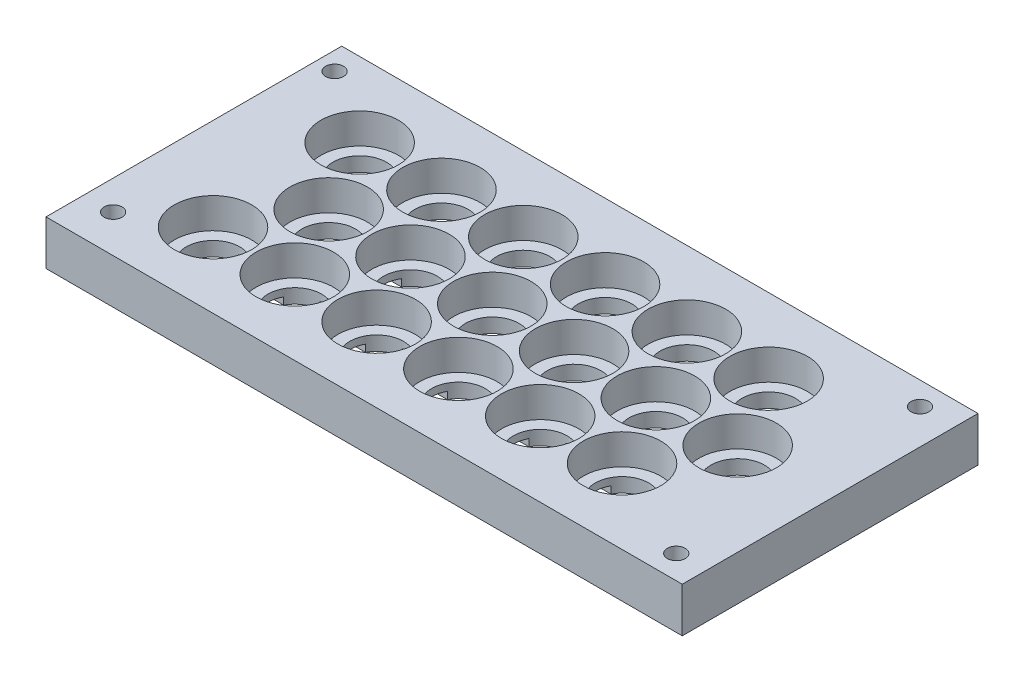
SolidWorks part; units mm, degrees
ref_plane "Front Plane" through (0, 0, 0) normal (0, 0, 1) x (1, 0, 0)
ref_plane "Top Plane" through (0, 0, 0) normal (0, 1, 0) x (1, 0, 0)
ref_plane "Right Plane" through (0, 0, 0) normal (1, 0, 0) x (0, 0, -1)
sketch "Sketch1" plane through (0, 0, 0) normal (0, 1, 0) x (1, 0, 0)
  line L0 (-11.825, 20.4815) -> (0, 0) construction
  line L5 (0, 0) -> (-11.825, -20.4815) construction
  line L6 (-11.825, -20.4815) -> (0, -20.4815) construction
  line L7 (0, -20.4815) -> (0, 20.4815) construction
  line L8 (0, 20.4815) -> (-11.825, 20.4815) construction
  line L9 (-11.825, 20.4815) -> (11.025, 20.4815) construction
  line L11 (140.075, -41.3065) -> (-37.65, -41.3065)
  line L12 (140.075, -41.3065) -> (140.075, 41.3065)
  line L13 (140.075, 41.3065) -> (-37.65, 41.3065)
  line L14 (-37.65, -41.3065) -> (-37.65, 41.3065)
  circle A0 centre (-11.825, 20.4815) radius 10.825
  circle A1 centre (0, 0) radius 10.825
  circle A2 centre (-11.825, -20.4815) radius 10.825
  circle A3 centre (11.025, 20.4815) radius 10.825
  circle A4 centre (22.85, 0) radius 10.825
  circle A5 centre (11.025, -20.4815) radius 10.825
  circle A6 centre (33.875, 20.4815) radius 10.825
  circle A7 centre (45.7, 0) radius 10.825
  circle A8 centre (33.875, -20.4815) radius 10.825
  circle A9 centre (56.725, 20.4815) radius 10.825
  circle A10 centre (68.55, 0) radius 10.825
  circle A11 centre (56.725, -20.4815) radius 10.825
  circle A12 centre (79.575, 20.4815) radius 10.825
  circle A13 centre (91.4, 0) radius 10.825
  circle A14 centre (79.575, -20.4815) radius 10.825
  circle A15 centre (102.425, 20.4815) radius 10.825
  circle A16 centre (114.25, 0) radius 10.825
  circle A17 centre (102.425, -20.4815) radius 10.825
  circle A18 centre (0, 0) radius 7.5
  circle A19 centre (-11.825, 20.4815) radius 7.5
  circle A20 centre (-11.825, -20.4815) radius 7.5
  circle A21 centre (11.025, 20.4815) radius 7.5
  circle A22 centre (22.85, 0) radius 7.5
  circle A23 centre (11.025, -20.4815) radius 7.5
  circle A24 centre (33.875, 20.4815) radius 7.5
  circle A25 centre (45.7, 0) radius 7.5
  circle A26 centre (33.875, -20.4815) radius 7.5
  circle A27 centre (56.725, 20.4815) radius 7.5
  circle A28 centre (68.55, 0) radius 7.5
  circle A29 centre (56.725, -20.4815) radius 7.5
  circle A30 centre (79.575, 20.4815) radius 7.5
  circle A31 centre (91.4, 0) radius 7.5
  circle A32 centre (79.575, -20.4815) radius 7.5
  circle A33 centre (102.425, 20.4815) radius 7.5
  circle A34 centre (114.25, 0) radius 7.5
  circle A35 centre (102.425, -20.4815) radius 7.5
  circle A36 centre (130.3198, 34.8476) radius 2.5
  circle A37 centre (-32.5448, 34.1925) radius 2.5
  circle A38 centre (131.797, -34.6966) radius 2.5
  circle A39 centre (-29.4432, -30.7721) radius 2.5
  dimension "D4" = 21.65
  dimension "D7" = 15
  dimension "D13" = 5
  dimension "D1" = 30
  dimension "D2" = 30
  dimension "D3" = 2
  dimension "D6" = 22.85
  dimension "D9" = 10
  dimension "D10" = 10
  dimension "D11" = 15
  dimension "D12" = 15
  dimension "D5" = 6
  dimension "D8" = 6
extrude "Boss-Extrude1" add sketch "Sketch1" along normal blind 12.5 contours L14 L11 L12 L13 A17 A16 A15 A14 A13 A12 A11 A10 A9 A8 A7 A6 A5 A4 A3 A2 A1 A0 region at (51.2125, 0, 39.3466)
extrude "Boss-Extrude2" add sketch "Sketch1<3>" along normal blind 4 contours A0 A19 | A2 A20 | A1 A18 | A3 A21 | A6 A24 | A4 A22 | A5 A23 | A8 A26 | A7 A25 | A9 A27 | A10 A28 | A11 A29 | A12 A30 | A15 A33 | A16 A34 | A13 A31 | A17 A35 | A14 A32 region at (-22.3438, 0, -20.4815) region at (-10.5188, 0, 0) region at (-22.3438, 0, 20.4815) region at (0.5062, 0, -20.4815) region at (12.3312, 0, 0) region at (0.5062, 0, 20.4815) region at (23.3562, 0, -20.4815) region at (35.1812, 0, 0) region at (23.3562, 0, 20.4815) region at (46.2062, 0, -20.4815) region at (58.0312, 0, 0) region at (46.2062, 0, 20.4815) region at (69.0562, 0, -20.4815) region at (80.8812, 0, 0) region at (69.0562, 0, 20.4815) region at (91.9062, 0, -20.4815) region at (103.7312, 0, 0) region at (91.9062, 0, 20.4815)
sketch "Sketch1<3>" plane through (0, 0, 0) normal (0, 1, 0) x (1, 0, 0) same geometry as "Sketch1"
sketch "Sketch3" plane through (0, 0, 0) normal (0, -1, 0) x (1, 0, 0)
  line L0 (-5.1918, 23.9815) -> (4.3918, 23.9815)
  line L3 (6.8184, 3.1241) -> (16.0316, 3.1241)
  line L4 (6.4209, -3.8759) -> (16.4291, -3.8759)
  line L5 (4.3977, 16.9702) -> (-5.1977, 16.9702)
  line L8 (-5.2252, 16.9188) -> (0.4002, 7.4893)
  line L9 (-12.2252, 12.9922) -> (-6.5998, 3.5627)
  line L10 (27.2477, 16.9702) -> (17.6523, 16.9702)
  line L11 (17.6582, 23.9815) -> (27.2418, 23.9815)
  line L12 (10.6248, 12.9922) -> (16.2502, 3.5627)
  line L13 (17.6248, 16.9188) -> (23.2502, 7.4893)
  line L14 (50.0977, 16.9702) -> (40.5023, 16.9702)
  line L15 (40.5082, 23.9815) -> (50.0918, 23.9815)
  line L16 (33.4748, 12.9922) -> (39.1002, 3.5627)
  line L17 (40.4748, 16.9188) -> (46.1002, 7.4893)
  line L18 (72.9477, 16.9702) -> (63.3523, 16.9702)
  line L19 (63.3582, 23.9815) -> (72.9418, 23.9815)
  line L20 (56.3248, 12.9922) -> (61.9502, 3.5627)
  line L21 (63.3248, 16.9188) -> (68.9502, 7.4893)
  line L22 (95.7977, 16.9702) -> (86.2023, 16.9702)
  line L23 (86.2082, 23.9815) -> (95.7918, 23.9815)
  line L24 (79.1748, 12.9922) -> (84.8002, 3.5627)
  line L25 (86.1748, 16.9188) -> (91.8002, 7.4893)
  arc A2 (6.4209, -3.8759) -> (6.8184, 3.1241) centre (0, 0) ccw
  circle A3 centre (0, 0) radius 7.5 construction
  arc A4 (16.0316, 3.1241) -> (16.4291, -3.8759) centre (22.85, 0) ccw
  circle A5 centre (22.85, 0) radius 7.5 construction
  arc A6 (-5.1918, 23.9815) -> (-5.1977, 16.9702) centre (-11.825, 20.4815) cw
  circle A7 centre (-11.825, 20.4815) radius 7.5 construction
  arc A8 (4.3918, 23.9815) -> (4.3977, 16.9702) centre (11.025, 20.4815) ccw
  circle A9 centre (11.025, 20.4815) radius 7.5 construction
  arc A14 (-5.2252, 16.9188) -> (-12.2252, 12.9922) centre (-11.825, 20.4815) cw
  arc A15 (0.4002, 7.4893) -> (-6.5998, 3.5627) centre (0, 0) ccw
  arc A16 (17.6582, 23.9815) -> (17.6523, 16.9702) centre (11.025, 20.4815) cw
  arc A17 (27.2418, 23.9815) -> (27.2477, 16.9702) centre (33.875, 20.4815) ccw
  arc A18 (23.2502, 7.4893) -> (16.2502, 3.5627) centre (22.85, 0) ccw
  arc A19 (17.6248, 16.9188) -> (10.6248, 12.9922) centre (11.025, 20.4815) cw
  arc A20 (40.5082, 23.9815) -> (40.5023, 16.9702) centre (33.875, 20.4815) cw
  arc A21 (50.0918, 23.9815) -> (50.0977, 16.9702) centre (56.725, 20.4815) ccw
  arc A22 (46.1002, 7.4893) -> (39.1002, 3.5627) centre (45.7, 0) ccw
  arc A23 (40.4748, 16.9188) -> (33.4748, 12.9922) centre (33.875, 20.4815) cw
  arc A24 (63.3582, 23.9815) -> (63.3523, 16.9702) centre (56.725, 20.4815) cw
  arc A25 (72.9418, 23.9815) -> (72.9477, 16.9702) centre (79.575, 20.4815) ccw
  arc A26 (68.9502, 7.4893) -> (61.9502, 3.5627) centre (68.55, 0) ccw
  arc A27 (63.3248, 16.9188) -> (56.3248, 12.9922) centre (56.725, 20.4815) cw
  arc A28 (86.2082, 23.9815) -> (86.2023, 16.9702) centre (79.575, 20.4815) cw
  arc A29 (95.7918, 23.9815) -> (95.7977, 16.9702) centre (102.425, 20.4815) ccw
  arc A30 (91.8002, 7.4893) -> (84.8002, 3.5627) centre (91.4, 0) ccw
  arc A31 (86.1748, 16.9188) -> (79.1748, 12.9922) centre (79.575, 20.4815) cw
  dimension "D1" = 7
  dimension "D2" = 3.5
  dimension "D4" = 7
extrude "Cut-Extrude2" cut sketch "Sketch3" against normal blind 2
equation "\"cell_spacing\"= 1.2"
equation "\"hole_diameter\"= 21.65"
equation "\"D6@Sketch1\"=\"cell_spacing\"+\"hole_diameter\""
equation "\"nipple\"= 15"
equation "\"D7@Sketch1\"=\"nipple\""
equation "\"side_spacing\"=10"
equation "\"D9@Sketch1\"=\"side_spacing\""
equation "\"D10@Sketch1\"=\"side_spacing\""
equation "\"end_spacing\"=15"
equation "\"D11@Sketch1\"=\"end_spacing\""
equation "\"D12@Sketch1\"=\"end_spacing\""
equation "\"bolt_hole\"=5"
equation "\"D13@Sketch1\"=\"bolt_hole\""
equation "\"channel_width\"=7"
equation "\"D1@Sketch3\"=\"channel_width\""
equation "\"D2@Sketch3\"=\"channel_width\"/2mm"
equation "\"D4@Sketch3\"=\"channel_width\""
